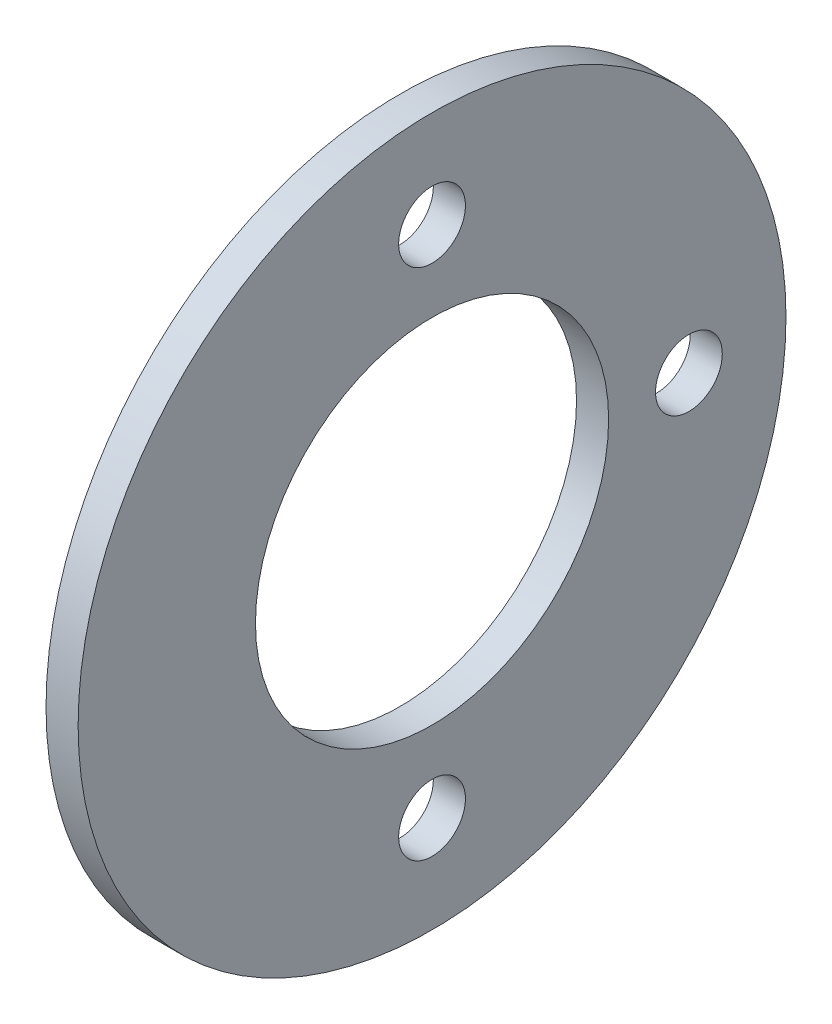
SolidWorks part; units mm, degrees
ref_plane "Front Plane" through (0, 0, 0) normal (0, 0, 1) x (1, 0, 0)
ref_plane "Top Plane" through (0, 0, 0) normal (0, 1, 0) x (1, 0, 0)
ref_plane "Right Plane" through (0, 0, 0) normal (1, 0, 0) x (0, 0, -1)
sketch "Sketch1" plane through (0, 0, 0) normal (1, 0, 0) x (0, 0, -1)
  circle A0 centre (0, 0) radius 17.4625
  circle A1 centre (0, 0) radius 35
  circle A2 centre (0, 25.4) radius 3.302
  circle A3 centre (25.4, 0) radius 3.302
  circle A4 centre (0, -25.4) radius 3.302
  circle A5 centre (-25.4, 0) radius 3.302 [skipped]
  dimension "D1" = 70
  dimension "D3" = 6.604
  dimension "D5" = 34.925
  dimension "D2" = 25.4
  dimension "D4" = 4
extrude "Boss-Extrude1" add sketch "Sketch1" along normal blind 3.175
